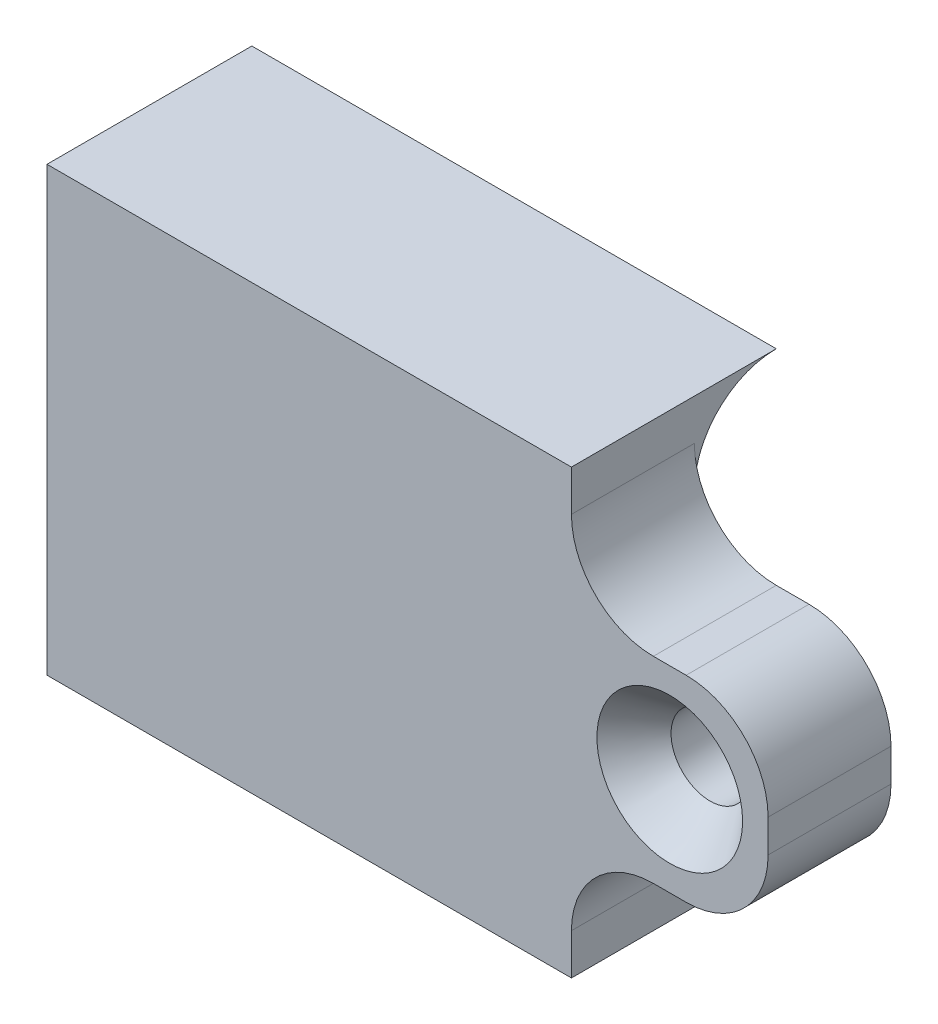
SolidWorks part; units mm, degrees
material "ABS"
ref_plane "Front" through (0, 0, 0) normal (0, 0, 1) x (1, 0, 0)
ref_plane "Top" through (0, 0, 0) normal (0, 1, 0) x (1, 0, 0)
ref_plane "Right" through (0, 0, 0) normal (1, 0, 0) x (0, 0, -1)
sketch "Sketch1" plane through (0, 0, 0) normal (0, 0, 1) x (1, 0, 0)
  line L1 (-6.4, 5.4) -> (6.4, 5.4)
  line L2 (-6.4, 5.4) -> (-6.4, -5.4)
  line L3 (-6.4, -5.4) -> (6.4, -5.4)
  line L4 (6.4, 5.4) -> (6.4, -5.4)
  line L5 (-6.4, 5.4) -> (6.4, -5.4) construction
  line L6 (-6.4, -5.4) -> (6.4, 5.4) construction
  line L7 (6.4, 2.4) -> (11.2, 2.4)
  line L8 (6.4, 2.4) -> (6.4, -2.4)
  line L9 (6.4, -2.4) -> (11.2, -2.4)
  line L10 (11.2, 2.4) -> (11.2, -2.4)
  point P0 (0, 0)
  point P10 (6.4, 0)
  point P11 (6.3095, 0)
  dimension "D1" = 12.8
  dimension "D2" = 10.8
  dimension "D3" = 4.8
extrude "Boss-Extrude1" add sketch "Sketch1" along normal mid plane 3 contours L4 L1 L2 L3 | L10 L7 L4 L9 region at (0, 0, 0) region at (8.8, 0, 0)
hole_wizard "#2 Clearance Hole1" positions "Sketch3" profile "Sketch2" hole size "#2" standard "ANSI Inch" end condition up to next
sketch "Sketch3" plane through (0, 0, 1.5) normal (0, 0, 1) x (1, 0, 0)
  line L0 (6.4, 2.4) -> (11.2, -2.4) construction
  point P0 (8.8, 0)
  point P9 (8.75, 0)
sketch "Sketch2" plane through (8.8, 0, 1.5) normal (1, 0, 0) x (0, -1, 0)
  line L0 (0, 0) -> (0, 3)
  line L1 (0, 3) -> (0.9525, 3)
  line L2 (0.9525, 3) -> (0.9525, 0.9838)
  line L3 (0.9525, 0.9838) -> (1.778, 0)
  line L5 (1.778, 0) -> (0, 0)
  line L6 (-0.9525, 0.9838) -> (-1.778, 0) construction
  line L11 (0, -6.35) -> (0, 107.95) construction
  dimension "Thru Hole Dia." = 1.905
  dimension "Thru Hole Depth" = 3
  dimension "Near C'Sink Dia." = 3.556
  dimension "Near C'Sink Angle" = 80
fillet "Fillet1" radius 2 4 edges at (11.2, -2.4, 0) (6.4, -2.4, 0) (11.2, 2.4, 0) (6.4, 2.4, 0)
sketch "Sketch4" plane through (0, 0, 0) normal (1, 0, 0) x (0, 0, -1)
  line L6 (1.5, 5.4) -> (3.5, 5.4)
  line L7 (1.5, 5.4) -> (1.5, 3.4)
  line L8 (1.5, 2.4) -> (1.5, 4.4) construction
  line L9 (50, 0) -> (-50, 0) construction
  line L10 (1.5, -5.4) -> (1.5, -3.4)
  line L11 (1.5, -5.4) -> (3.5, -5.4)
  arc A2 (1.5, 3.4) -> (3.5, 5.4) centre (3.5, 3.4) cw
  arc A3 (1.5, -3.4) -> (3.5, -5.4) centre (3.5, -3.4) ccw
  dimension "D1" = 2
extrude "Boss-Extrude2" add sketch "Sketch4" against normal up to surface and the other way up to surface up to face at (-6.4, 0, 0) other way up to face at (6.4, 4.9, 0)
